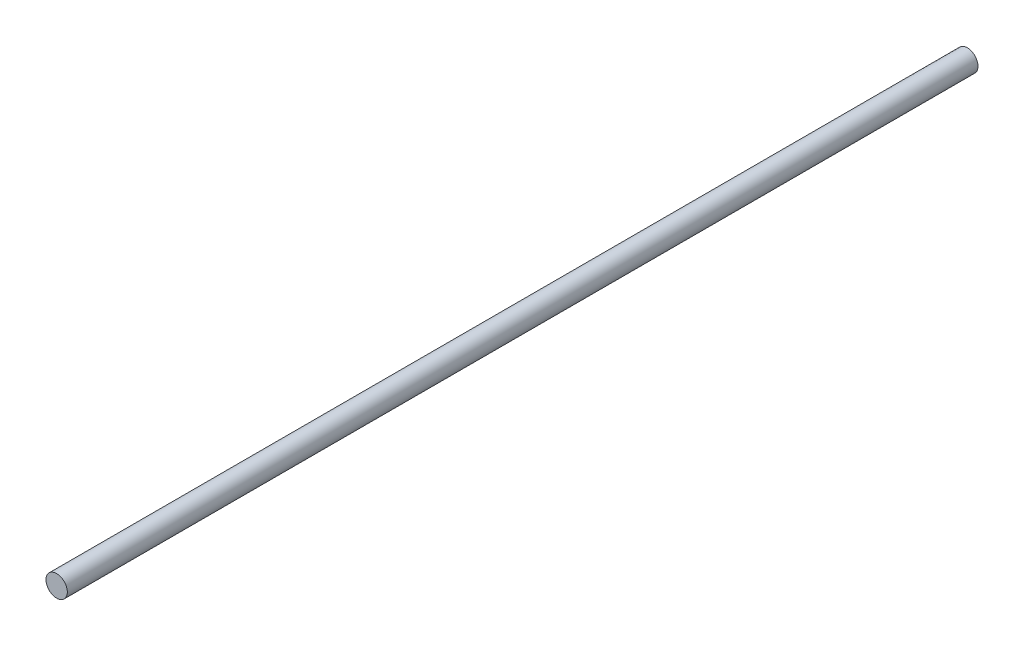
SolidWorks part; units mm, degrees
ref_plane "Front Plane" through (0, 0, 0) normal (0, 0, 1) x (1, 0, 0)
ref_plane "Top Plane" through (0, 0, 0) normal (0, 1, 0) x (1, 0, 0)
ref_plane "Right Plane" through (0, 0, 0) normal (1, 0, 0) x (0, 0, -1)
sketch "Sketch1" plane through (0, 0, 0) normal (0, 0, 1) x (1, 0, 0)
  circle A0 centre (0, 0) radius 4.3
extrude "Boss-Extrude1" add sketch "Sketch1" along normal blind 367
ref_axis "Axis1" through (0, 0, 367) along (0, 0, -1)
